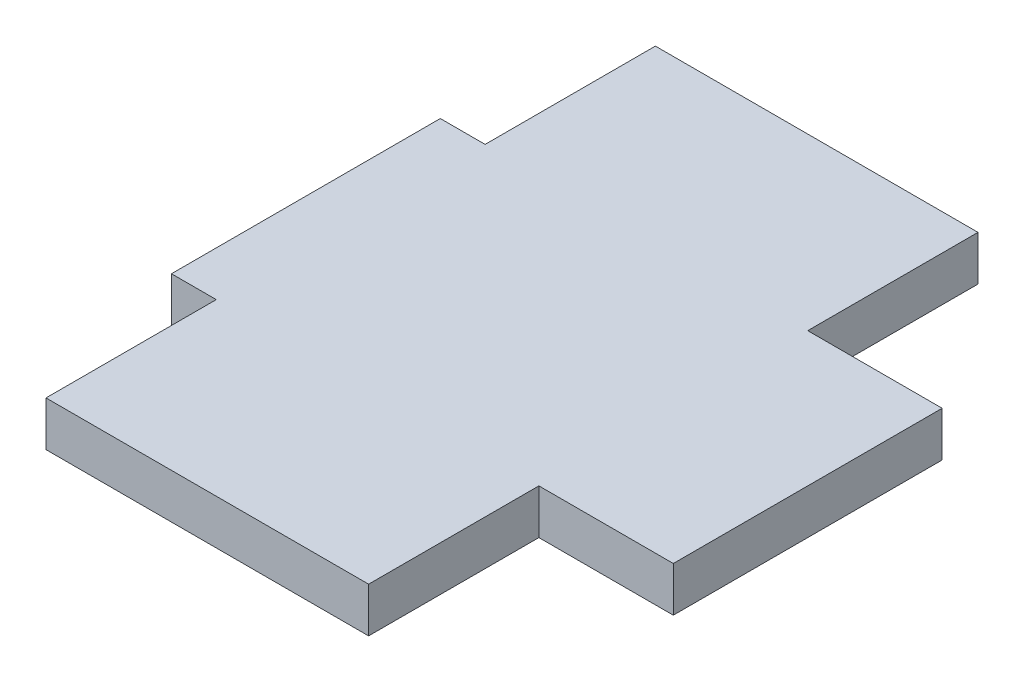
SolidWorks part; units mm, degrees
ref_plane "Front" through (0, 0, 0) normal (0, 0, 1) x (1, 0, 0)
ref_plane "Top" through (0, 0, 0) normal (0, 1, 0) x (1, 0, 0)
ref_plane "Right" through (0, 0, 0) normal (1, 0, 0) x (0, 0, -1)
sketch "Sketch1" plane through (0, 0, 0) normal (0, 1, 0) x (1, 0, 0)
  line L0 (11.43, 43.18) -> (11.43, 0) construction
  line L1 (0, 0) -> (22.86, 0)
  line L2 (0, 0) -> (0, 12.065)
  line L3 (0, 43.18) -> (22.86, 43.18)
  line L4 (22.86, 0) -> (22.86, 12.065)
  line L5 (0, 12.065) -> (-3.175, 12.065)
  line L7 (0, 31.115) -> (-3.175, 31.115)
  line L8 (-3.175, 12.065) -> (-3.175, 31.115)
  line L9 (0, 31.115) -> (0, 43.18)
  line L10 (22.86, 31.115) -> (22.86, 43.18)
  line L11 (22.86, 12.065) -> (32.385, 12.065)
  line L13 (22.86, 31.115) -> (32.385, 31.115)
  line L14 (32.385, 12.065) -> (32.385, 31.115)
  point P11 (-3.175, 21.59)
  point P12 (11.43, 21.59)
  dimension "D1" = 22.86
  dimension "D2" = 43.18
  dimension "D3" = 19.05
  dimension "D4" = 3.175
  dimension "D5" = 9.525
extrude "Boss-Extrude1" add sketch "Sketch1" along normal blind 3.175
